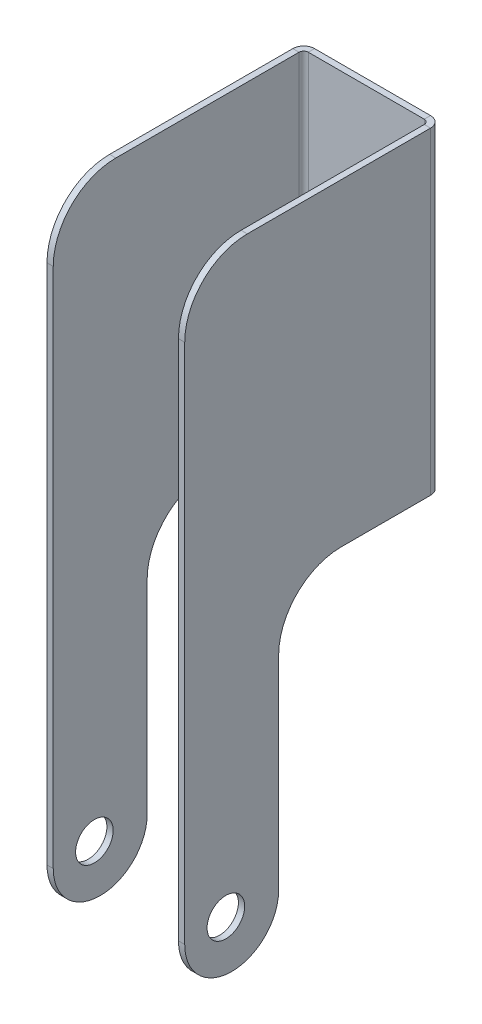
SolidWorks part; units mm, degrees
note: The reader was unsure of these and kept them because the rebuilt part matched: flange length of "Brida de arista1".
ref_plane "Alzado" through (0, 0, 0) normal (0, 0, 1) x (1, 0, 0)
ref_plane "Planta" through (0, 0, 0) normal (0, 1, 0) x (1, 0, 0)
ref_plane "Vista lateral" through (0, 0, 0) normal (1, 0, 0) x (0, 0, -1)
sketch "Croquis1" plane through (0, 0, 0) normal (0, 0, 1) x (1, 0, 0)
  line L1 (-10, -25.4) -> (10, -25.4)
  line L2 (-10, -25.4) -> (-10, 25.4)
  line L3 (-10, 25.4) -> (10, 25.4)
  line L4 (10, -25.4) -> (10, 25.4)
  line L5 (-10, -25.4) -> (10, 25.4) construction
  line L6 (-10, 25.4) -> (10, -25.4) construction
  point P0 (0, 0)
  dimension "D1" = 20
  dimension "D2" = 50.8
base flange "Brida base1" sketch "Croquis1" thickness 1 reverse thickness direction no parameters "D1"=0.7366
edge flange "Brida de arista1" sketch "Croquis10" flange profiles "Croquis10", "Croquis11" flange angle 90 flange length 40 bend radius 0.7366 thickness 1 parameters "D6"=10, "D8"=1
sketch "Croquis10" plane through (-10, 0, 0) normal (-1, 0, 0) x (0, -1, 0)
  line L2 (-25.4, 0) -> (-25.4, 40)
  line L3 (-25.4, 40) -> (25.4, 40)
  line L4 (25.4, 40) -> (25.4, 0)
  line L11 (-25.4, 0) -> (25.4, 0) construction
  line L12 (-25.4, 0) -> (25.4, 0)
sketch "Croquis11" plane through (10, 0, 0) normal (1, 0, 0) x (0, 1, 0)
  line L2 (25.4, 0) -> (25.4, 40)
  line L3 (25.4, 40) -> (-25.4, 40)
  line L4 (-25.4, 40) -> (-25.4, 0)
  line L9 (-25.4, 0) -> (25.4, 0) construction
  line L10 (-25.4, 0) -> (25.4, 0)
bend "Pliegue de arista1" bend radius 0.7366 bend angle 90 parameters "D5"=1
bend "Pliegue de arista2" bend radius 0.7366 bend angle 90 parameters "D5"=2
sketch "Croquis14" plane through (-11, 0, 0) normal (-1, 0, 0) x (0, 0, 1)
  line L0 (40, -25.4) -> (40, -75.4)
  line L1 (40, -75.4) -> (25, -75.4)
  line L2 (25, -75.4) -> (25, -25.4)
  line L3 (0.7366, -25.4) -> (40, -25.4) construction
  line L4 (25, -25.4) -> (40, -25.4)
  dimension "D1" = 50
  dimension "D2" = 15
base flange "Pestaña1" sketch "Croquis14" thickness 1 reverse thickness direction no parameters "D1"=0.7366
mirror "Simetría1" about plane through (0, 0, 0) normal (1, 0, 0) of "Pestaña1"
sketch "Croquis17" plane through (-11, 0, 0) normal (-1, 0, 0) x (0, 0, 1)
  line L0 (-1, -25.4) -> (-1, 25.4) construction
  line L1 (25, -75.4) -> (40, -75.4) construction
  circle A0 centre (33.4285, -67.4) radius 3
  dimension "D1" = 6
  dimension "D2" = 34.4285
  dimension "D3" = 8
extrude "Cortar-Extruir1" cut sketch "Croquis17" against normal through all
fillet "Redondeo1" radius 10 4 edges at (10.5, -25.4, 25) (-10.5, -25.4, 25) (10.5, 25.4, 40) (-10.5, 25.4, 40)
fillet "Redondeo2" radius 7.5 4 edges at (10.5, -75.4, 25) (10.5, -75.4, 40) (-10.5, -75.4, 25) (-10.5, -75.4, 40)
unfold "Desdoblar1" [suppressed]
sketch "Croquis14-1" plane through (-10.4692, 0, -1) normal (0, 0, -1) x (-1, 0, 0)
  line L0 (40, -25.4) -> (40, -75.4)
  line L1 (40, -75.4) -> (25, -75.4)
  line L2 (25, -75.4) -> (25, -25.4)
  line L4 (25, -25.4) -> (40, -25.4)
  dimension "D1" = 50
  dimension "D2" = 15
sketch "Croquis17-1" plane through (-10.4692, 0, -1) normal (0, 0, -1) x (-1, 0, 0)
  line L0 (-1.2058, -25.4) -> (-1.2058, 25.4) construction
  line L1 (25, -75.4) -> (40, -75.4) construction
  circle A0 centre (33.4285, -67.4) radius 3
  dimension "D1" = 6
  dimension "D2" = 34.6343
  dimension "D3" = 8
ref_point "Point1"
sketch "Líneas de pliegue1" [suppressed] plane through (0, 0, 0) normal (0, 1, 0) x (1, 0, 0)
sketch "Cuadro delimitador1" [suppressed] plane through (0, 0, 0) normal (0, 1, 0) x (1, 0, 0)
sheet metal parameters "Chapa metálica1" thickness 1 parameters "D1"=0.7366
flat pattern "Chapa desplegada1"
sketch "Líneas de pliegue2" plane through (0, 0, 0) normal (0, 1, 0) x (1, 0, 0)
sketch3d "Cuadro delimitador2" [suppressed]
  line L0 (-10, 25.4, 0) -> (-10, -25.4, 0) construction
  line L1 (10, 25.4, 0) -> (10, -25.4, 0) construction
  line L2 (-10, 25.4, 0) -> (10, 25.4, 0) construction
  line L3 (-10, -25.4, 0) -> (10, -25.4, 0) construction
sheet metal parameters "Chapa metálica2" thickness 1 parameters "D1"=0.7366
flat pattern "Chapa desplegada1"
sketch "Líneas de pliegue2" plane through (0, 0, 0) normal (0, 0, 1) x (1, 0, 0)
  line L0 (10.2346, -25.4) -> (10.2346, 25.4) construction
  line L1 (-10.2346, 25.4) -> (-10.2346, -25.4) construction
  line L2 (10.2346, -25.4) -> (10.2346, 25.4) construction
  line L3 (-10.2346, 25.4) -> (-10.2346, -25.4) construction
sketch3d "Cuadro delimitador2" [suppressed]
  line L0 (-50.4692, -25.4, 0) -> (50.4692, -25.4, 0) construction
  line L1 (-50.4692, 25.4, 0) -> (50.4692, 25.4, 0) construction
  line L2 (-50.4692, -25.4, 0) -> (-50.4692, 25.4, 0) construction
  line L3 (50.4692, -25.4, 0) -> (50.4692, 25.4, 0) construction
bend of the flat pattern "Aplanar-<Pliegue de arista1>1"
bend of the flat pattern "Aplanar-<Pliegue de arista2>1"
sheet metal parameters "Chapa metálica3" thickness 1 parameters "D1"=0.7366
flat pattern "Chapa desplegada3"
sketch "Líneas de pliegue3" plane through (0, 0, 0) normal (0, 0, 1) x (1, 0, 0)
  line L0 (10.2346, -25.4) -> (10.2346, 25.4) construction
  line L1 (-10.2346, 25.4) -> (-10.2346, -25.4) construction
  line L2 (10.2346, -25.4) -> (10.2346, 25.4) construction
  line L3 (-10.2346, 25.4) -> (-10.2346, -25.4) construction
sketch3d "Cuadro delimitador3" [suppressed]
  line L0 (-50.4692, -75.4, 0) -> (50.4692, -75.4, 0) construction
  line L1 (-50.4692, 25.4, 0) -> (50.4692, 25.4, 0) construction
  line L2 (-50.4692, -75.4, 0) -> (-50.4692, 25.4, 0) construction
  line L3 (50.4692, -75.4, 0) -> (50.4692, 25.4, 0) construction
bend of the flat pattern "Aplanar-<Pliegue de arista2>2"
bend of the flat pattern "Aplanar-<Pliegue de arista1>2"
sheet metal parameters "Chapa metálica4" thickness 1 parameters "D1"=0.7366
flat pattern "Chapa desplegada3"
sketch "Líneas de pliegue3" plane through (0, 0, 0) normal (0, 0, 1) x (1, 0, 0)
  line L0 (10.2346, -25.4) -> (10.2346, 25.4) construction
  line L1 (-10.2346, 25.4) -> (-10.2346, -25.4) construction
  line L2 (10.2346, -25.4) -> (10.2346, 25.4) construction
  line L3 (-10.2346, 25.4) -> (-10.2346, -25.4) construction
sketch3d "Cuadro delimitador3" [suppressed]
  line L0 (-50.4692, -75.4, 0) -> (50.4692, -75.4, 0) construction
  line L1 (-50.4692, 25.4, 0) -> (50.4692, 25.4, 0) construction
  line L2 (-50.4692, -75.4, 0) -> (-50.4692, 25.4, 0) construction
  line L3 (50.4692, -75.4, 0) -> (50.4692, 25.4, 0) construction
bend of the flat pattern "Aplanar-<Pliegue de arista2>2"
bend of the flat pattern "Aplanar-<Pliegue de arista1>2"
sheet metal parameters "Chapa metálica5" thickness 1 parameters "D1"=0.7366
flat pattern "Chapa desplegada3"
sketch "Líneas de pliegue3" plane through (0, 0, 0) normal (0, 0, 1) x (1, 0, 0)
  line L0 (10.2346, -25.4) -> (10.2346, 25.4) construction
  line L1 (-10.2346, 25.4) -> (-10.2346, -25.4) construction
  line L2 (10.2346, -25.4) -> (10.2346, 25.4) construction
  line L3 (-10.2346, 25.4) -> (-10.2346, -25.4) construction
sketch3d "Cuadro delimitador3" [suppressed]
  line L0 (-50.4692, -75.4, 0) -> (50.4692, -75.4, 0) construction
  line L1 (-50.4692, 25.4, 0) -> (50.4692, 25.4, 0) construction
  line L2 (-50.4692, -75.4, 0) -> (-50.4692, 25.4, 0) construction
  line L3 (50.4692, -75.4, 0) -> (50.4692, 25.4, 0) construction
bend of the flat pattern "Aplanar-<Pliegue de arista2>2"
bend of the flat pattern "Aplanar-<Pliegue de arista1>2"
